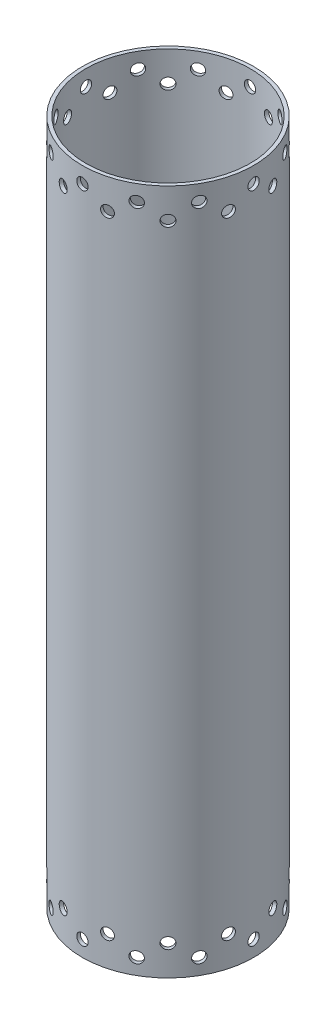
SolidWorks part; units mm, degrees
material "6061-T6 (SS)"
ref_plane "Front Plane" through (0, 0, 0) normal (0, 0, 1) x (1, 0, 0)
ref_plane "Top Plane" through (0, 0, 0) normal (0, 1, 0) x (1, 0, 0)
ref_plane "Right Plane" through (0, 0, 0) normal (1, 0, 0) x (0, 0, -1)
sketch "Sketch2" plane through (0, 0, 0) normal (0, 1, 0) x (1, 0, 0)
  circle A0 centre (0, 0) radius 76.2
  circle A1 centre (0, 0) radius 73.025
  dimension "D1" = 152.4
  dimension "D2" = 3.175
extrude "Boss-Extrude1" add sketch "Sketch2" along normal blind 609.6
sketch "Sketch3" plane through (0, 0, 0) normal (0, 0, 1) x (1, 0, 0)
  line L0 (0, 609.6) -> (0, 595.503) construction
  line L1 (73.025, 609.6) -> (-73.025, 609.6) construction
  circle A0 centre (0, 595.503) radius 5.0419
  dimension "D1" = 10.0838
  dimension "D2" = 14.097
extrude "Cut-Extrude1" cut sketch "Sketch3" against normal blind 1143
ref_plane "Plane1" through (-19.722, 0, 73.6035) normal (-0.2588, 0, 0.9659) x (0, -1, 0)
sketch "Sketch6" plane through (-19.722, 0, 73.6035) normal (-0.2588, 0, 0.9659) x (0, -1, 0)
  line L0 (-609.6, 0) -> (-582.803, 0) construction
  line L1 (-609.6, 76.2) -> (-609.6, -76.2) construction
  circle A0 centre (-582.803, 0) radius 5.0419
  dimension "D1" = 10.0838
  dimension "D2" = 26.797
extrude "Cut-Extrude2" cut sketch "Sketch6" against normal blind 25.4
pattern_circular "CirPattern2" count 12 over 360 about axis through (0, 609.6, 0) along (0, -1, 0) of "Cut-Extrude2", "Cut-Extrude1"
ref_plane "Plane2" through (0, 304.8, 0) normal (0, 1, 0) x (1, 0, 0)
mirror "Mirror1" about plane through (0, 304.8, 0) normal (0, 1, 0) of "CirPattern2"
equation "\"holeDia\"=0.397"
equation "\"D1@Sketch3\"=\"holeDia\""
equation "\"D1@Sketch6\"=\"holeDia\""
equation "\"numHoles\"=12"
equation "\"D1@CirPattern2\"=\"numHoles\""
equation "\"D1@Plane1\"=180/\"numHoles\""
equation "\"D2@Sketch6\"=\"D2@Sketch3\"+.5"
